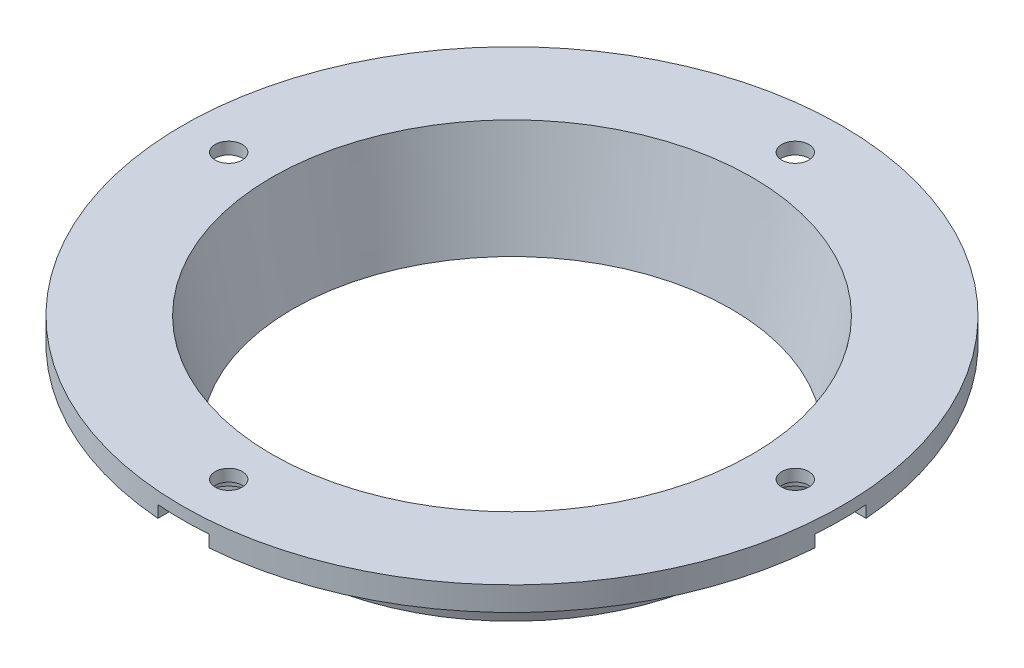
SolidWorks part; units mm, degrees
ref_plane "Front Plane" through (0, 0, 0) normal (0, 0, 1) x (1, 0, 0)
ref_plane "Top Plane" through (0, 0, 0) normal (0, 1, 0) x (1, 0, 0)
ref_plane "Right Plane" through (0, 0, 0) normal (1, 0, 0) x (0, 0, -1)
sketch "Sketch2" plane through (0, 0, 0) normal (0, 0, 1) x (1, 0, 0)
  line L0 (3.4238, 17.6286) -> (3.4238, 30.6286)
  line L1 (-37.8762, 30.6286) -> (-27.0762, 30.6286)
  line L2 (-37.8762, 30.6286) -> (-37.8762, 27.6286)
  line L3 (-37.8762, 27.6286) -> (-27.0762, 27.6286)
  line L4 (-27.0762, 30.6286) -> (-27.0762, 27.6286)
  line L5 (-27.0762, 30.6286) -> (-26.6564, 30.6286)
  line L6 (-25.0762, 17.6286) -> (-27.0762, 27.6286)
  line L7 (-26.6564, 30.6286) -> (-24.0564, 17.6286)
  line L8 (-24.0564, 17.6286) -> (-25.0762, 17.6286)
revolve "Revolve1" add sketch "Sketch2" angle 360 about L0 region at (-32.4762, 29.1286, 0) region at (-25.7636, 23.728, 0)
sketch "Sketch3" plane through (0, 27.6286, 0) normal (0, -1, 0) x (1, 0, 0)
  line L0 (44.5997, -3.2) -> (38.9238, -3.2)
  line L1 (38.9238, 3.2) -> (44.5997, 3.2)
  line L2 (6.6238, 41.1758) -> (6.6238, 35.5)
  line L3 (0.2238, 35.5) -> (0.2238, 41.1758)
  line L4 (-37.752, 3.2) -> (-32.0762, 3.2)
  line L5 (-32.0762, -3.2) -> (-37.752, -3.2)
  line L6 (0.2238, -41.1758) -> (0.2238, -35.5)
  line L7 (6.6238, -35.5) -> (6.6238, -41.1758)
  circle A0 centre (3.4238, 35.5) radius 1.7
  circle A1 centre (-32.0762, 0) radius 1.7
  circle A2 centre (3.4238, -35.5) radius 1.7
  circle A3 centre (38.9238, 0) radius 1.7
  arc A4 (38.9238, 3.2) -> (38.9238, -3.2) centre (38.9238, 0) ccw
  arc A5 (44.5997, 3.2) -> (6.6238, 41.1758) centre (3.4238, 0) ccw
  arc A6 (0.2238, 35.5) -> (6.6238, 35.5) centre (3.4238, 35.5) ccw
  arc A7 (0.2238, 41.1758) -> (-37.752, 3.2) centre (3.4238, 0) ccw
  arc A8 (-32.0762, -3.2) -> (-32.0762, 3.2) centre (-32.0762, 0) ccw
  arc A9 (-37.752, -3.2) -> (0.2238, -41.1758) centre (3.4238, 0) ccw
  arc A10 (6.6238, -35.5) -> (0.2238, -35.5) centre (3.4238, -35.5) ccw
  arc A11 (6.6238, -41.1758) -> (44.5997, -3.2) centre (3.4238, 0) ccw
  circle A12 centre (3.4238, 0) radius 41.3 construction
  circle A13 centre (3.4238, 0) radius 41.3
  circle M2 centre (3.4238, 0) radius 41.3
extrude "Cut-Extrude1" cut sketch "Sketch3" against normal blind 1.5 contours L3 A6 L2 A0 M2 | L1 A4 L0 A3 M2 | L5 A8 L4 A1 M2 | L7 A10 L6 A2 M2 region at (40.8453, 27.6286, 0) region at (3.4238, 27.6286, -37.4215) region at (-33.9976, 27.6286, 0) region at (3.4238, 27.6286, 37.4215)
extrude "Cut-Extrude2" cut sketch "Sketch3<3>" against normal through all contours A0 | A2 | A1 | A3 region at (3.4238, 27.6286, 35.5) region at (-32.0762, 27.6286, 0) region at (3.4238, 27.6286, -35.5)
sketch "Sketch3<3>" plane through (0, 27.6286, 0) normal (0, -1, 0) x (1, 0, 0) same geometry as "Sketch3"
